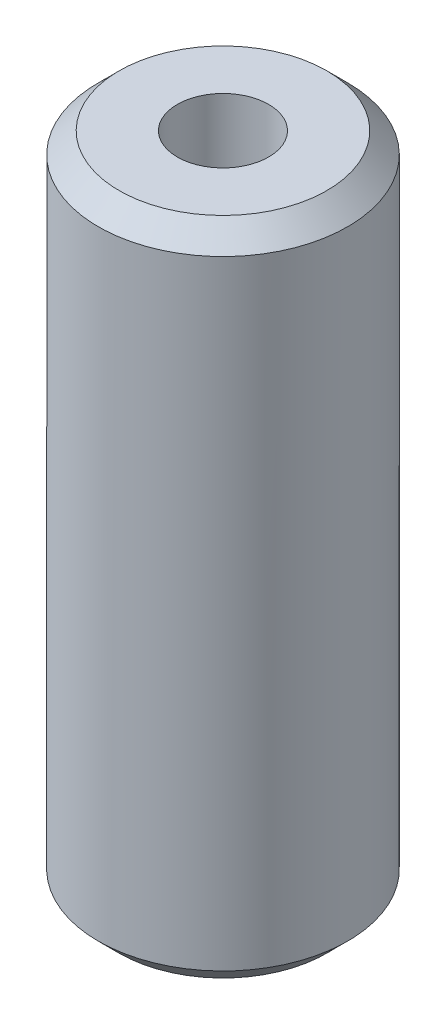
SolidWorks part; units mm, degrees
ref_plane "Front Plane" through (0, 0, 0) normal (0, 0, 1) x (1, 0, 0)
ref_plane "Top Plane" through (0, 0, 0) normal (0, 1, 0) x (1, 0, 0)
ref_plane "Right Plane" through (0, 0, 0) normal (1, 0, 0) x (0, 0, -1)
sketch "Sketch1" plane through (0, 0, 0) normal (0, 1, 0) x (1, 0, 0)
  circle A0 centre (0, 0) radius 30
  dimension "SHAFT_OD" = 60
extrude "Boss-Extrude1" add sketch "Sketch1" along normal blind 158.9104
sketch "Sketch2" plane through (0, 0, 0) normal (0, 1, 0) x (1, 0, 0)
  circle A0 centre (0, 0) radius 10.9834
  dimension "BORE_D" = 21.9669
extrude "Cut-Extrude1" cut sketch "Sketch2" along normal through all
chamfer "Chamfer1" distance 5.0181 angle 45 2 edges at (0, 158.9104, 30) (0, 0, 30)
